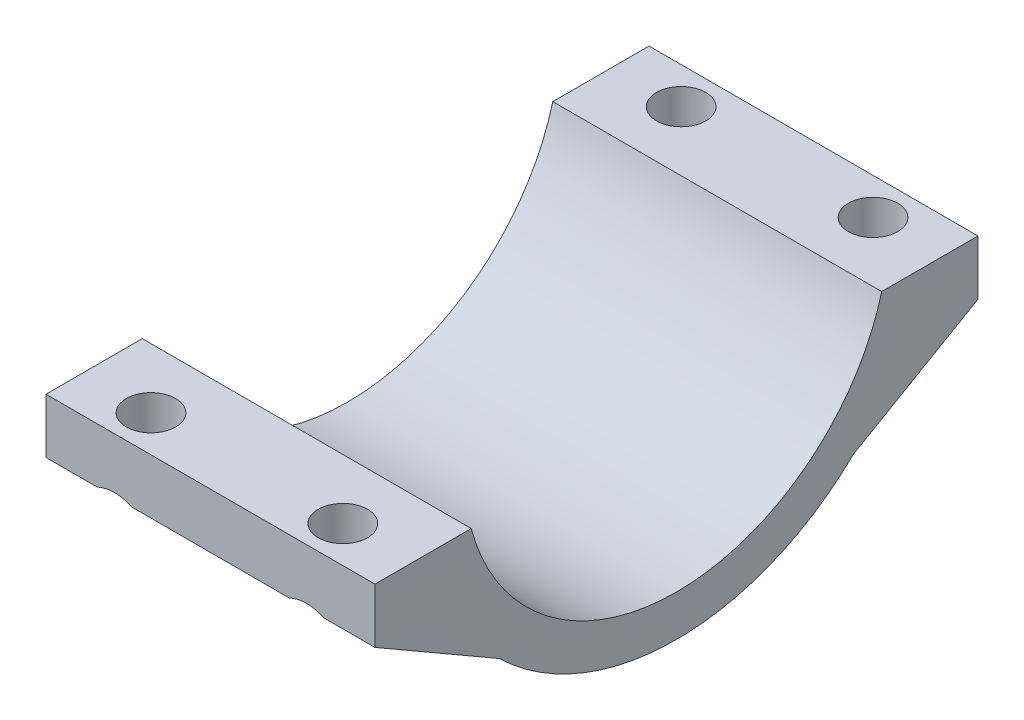
SolidWorks part; units mm, degrees
ref_plane "前视基准面" through (0, 0, 0) normal (0, 0, 1) x (1, 0, 0)
ref_plane "上视基准面" through (0, 0, 0) normal (0, 1, 0) x (1, 0, 0)
ref_plane "右视基准面" through (0, 0, 0) normal (1, 0, 0) x (0, 0, -1)
sketch "草图1" plane through (0, 0, 0) normal (1, 0, 0) x (0, 0, -1)
  line L0 (0, 0) -> (0, -4) construction
  line L1 (-22, -4) -> (-14.975, -4) construction
  line L2 (0, -4) -> (14.975, -4) construction
  line L3 (-22, -4) -> (-14.975, -4)
  line L4 (-22, -4) -> (-22, -8)
  line L5 (-22, -8) -> (-16.6808, -8)
  line L6 (22, -4) -> (22, -8)
  line L7 (14.975, -4) -> (22, -4) construction
  line L8 (0, -4) -> (14.975, -4) construction
  line L9 (14.975, -4) -> (22, -4)
  line L10 (-13.2759, -8) -> (13.2759, -8) construction
  line L11 (16.6808, -8) -> (22, -8)
  line L12 (13.2759, -8) -> (16.6808, -8) construction
  line L13 (-16.6808, -8) -> (-13.2759, -8) construction
  line L14 (-14.975, -4) -> (0, -4) construction
  line L15 (-14.975, -4) -> (0, -4) construction
  arc A0 (-14.975, -4) -> (14.975, -4) centre (0, 0) ccw
  arc A1 (-16.6808, -8) -> (16.6808, -8) centre (0, 0) ccw
  arc A2 (18.0624, -4) -> (-18.0624, -4) centre (0, 0) ccw construction
  arc A3 (14.975, -4) -> (-14.975, -4) centre (0, 0) ccw construction
  arc A4 (-18.0624, -4) -> (-16.6808, -8) centre (0, 0) ccw construction
  arc A5 (16.6808, -8) -> (18.0624, -4) centre (0, 0) ccw construction
  point P7 (0, -4)
  dimension "D1" = 31
  dimension "D4" = 37
  dimension "D2" = 44
  dimension "D3" = 4
  dimension "D5" = 4
extrude "凸台-拉伸1" add sketch "草图1" along normal blind 24
sketch "草图2" plane through (0, -8, 0) normal (0, -1, 0) x (1, 0, 0)
  line L0 (12, 22) -> (12, 16.6808) construction
  line L1 (24, 22) -> (0, 22) construction
  line L2 (24, 16.6808) -> (0, 16.6808) construction
  line L3 (0, 19.3404) -> (12, 19.3404) construction
  line L4 (0, 22) -> (0, 16.6808) construction
  circle A1 centre (5, 19.3404) radius 1.5
  circle A2 centre (19, 19.3404) radius 1.5
  dimension "D1" = 3
  dimension "D2" = 14
sketch "草图3" plane through (0, 0, 0) normal (-1, 0, 0) x (0, 0, 1)
  line L0 (22, -8) -> (12.9166, -13.2443)
  line L1 (22, -8) -> (16.6808, -8) construction
  arc A0 (-16.6808, -8) -> (16.6808, -8) centre (0, 0) ccw construction
  dimension "D1" = 30
rib "筋1" sketch "草图3" sketch "草图3" thickness 2 extrusion direction parallel to sketch draft on no parameters "D1"=2
ref_plane "基准面1" through (12, 0, 0) normal (-1, 0, 0) x (0, 0, -1)
sketch "草图4" plane through (12, 0, 0) normal (-1, 0, 0) x (0, 0, -1)
  line L0 (-22, 8) -> (-12.9166, 13.2443) construction
  line L1 (-22, 8) -> (-12.9166, 13.2443)
rib "筋2" sketch "草图4" sketch "草图4" thickness 8 extrusion direction parallel to sketch draft on no parameters "D1"=8
mirror "镜向1" about plane through (12, 0, 0) normal (-1, 0, 0) of "筋1"
ref_plane "基准面2" through (0, 0, 0) normal (0, 0, 1) x (1, 0, 0)
hole_wizard "打孔尺寸(%根据十字)槽沉头木螺钉的类型1" positions "草图5" profile "草图6" countersink size "M3" standard "GB"
sketch "草图5" plane through (0, -8, 0) normal (0, -1, 0) x (-1, 0, 0)
  point P0 (-19, -19.3404)
  point P3 (-5, -19.3404)
sketch "草图6" plane through (19, -8, 19.3404) normal (1, 0, 0) x (0, 0, -1)
  line L0 (0, 0) -> (0, 6.0815)
  line L1 (0, 6.0815) -> (1.8, 5)
  line L2 (1.8, 5) -> (1.8, 1.15)
  line L3 (1.8, 1.15) -> (2.95, 0)
  line L5 (2.95, 0) -> (0, 0)
  line L6 (-1.8, 1.15) -> (-2.95, 0) construction
  line L10 (0, 6.0815) -> (-1.8, 5) construction
  line L11 (0, -6.35) -> (0, 107.95) construction
  dimension "孔直径" = 3.6
  dimension "孔深度" = 5
  dimension "近端锥形沉头孔直径" = 5.9
  dimension "近端锥形沉头孔角度" = 90
  dimension "导头角度" = 118
mirror "镜向2" about plane through (0, 0, 0) normal (0, 0, 1) of "筋1", "镜向1", "打孔尺寸(%根据十字)槽沉头木螺钉的类型1", "筋2"
